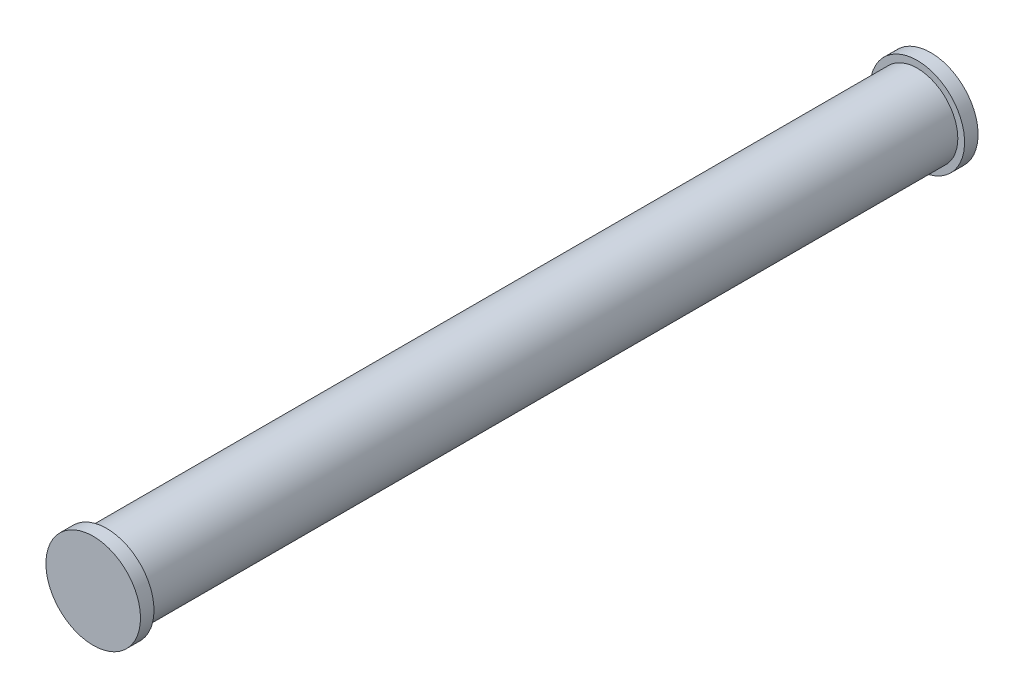
SolidWorks part; units mm, degrees
ref_plane "Front Plane" through (0, 0, 0) normal (0, 0, 1) x (1, 0, 0)
ref_plane "Top Plane" through (0, 0, 0) normal (0, 1, 0) x (1, 0, 0)
ref_plane "Right Plane" through (0, 0, 0) normal (1, 0, 0) x (0, 0, -1)
sketch "Sketch1" plane through (0, 0, 0) normal (0, 0, 1) x (1, 0, 0)
  circle A0 centre (0, 0) radius 3
  dimension "D1" = 6
extrude "Boss-Extrude1" add sketch "Sketch1" along normal blind 30 and the other way blind 30
sketch "Sketch2" plane through (0, 0, 30) normal (0, 0, 1) x (1, 0, 0)
  circle A0 centre (0, 0) radius 3.5
  dimension "D1" = 7
extrude "Boss-Extrude2" add sketch "Sketch2" along normal blind 1
sketch "Sketch3" plane through (0, 0, -30) normal (0, 0, -1) x (-1, 0, 0)
  circle A1 centre (0, 0) radius 3.5
  circle A2 centre (0, 0) radius 3.5
  dimension "D1" = 0
extrude "Boss-Extrude3" add sketch "Sketch3" along normal blind 1
